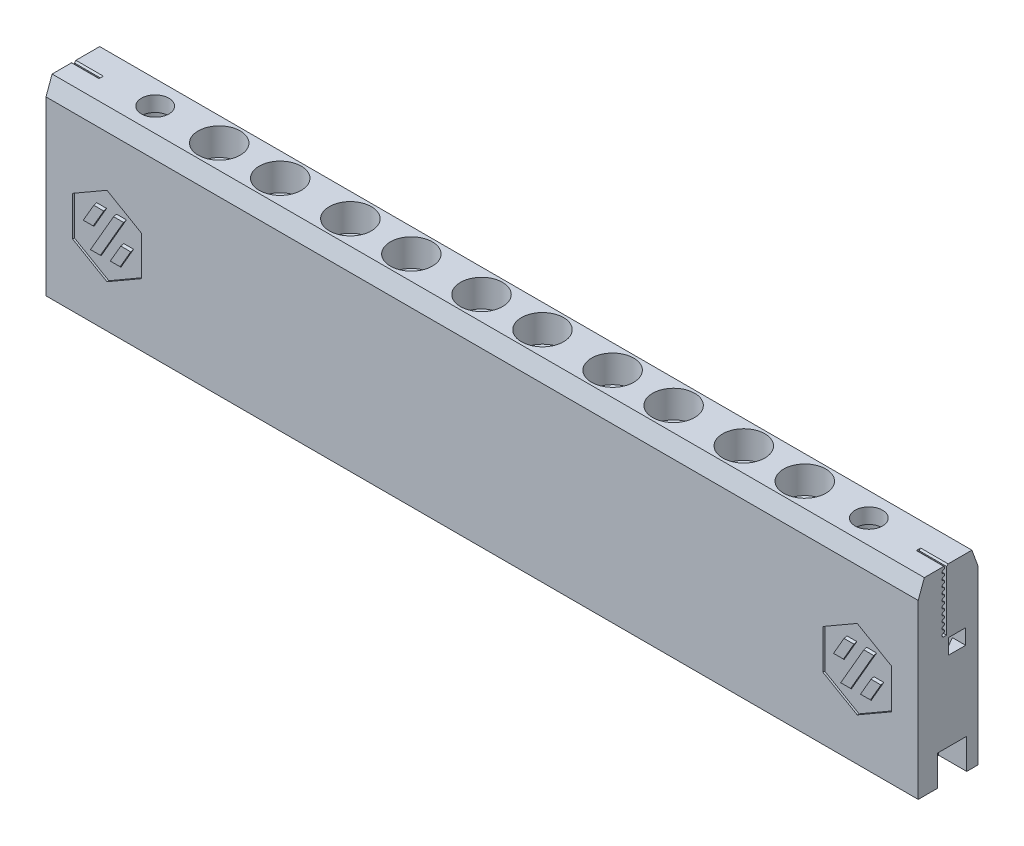
SolidWorks part; units mm, degrees
material "ABS"
ref_plane "Ebene vorne" through (0, 0, 0) normal (0, 0, 1) x (1, 0, 0)
ref_plane "Ebene oben" through (0, 0, 0) normal (0, 1, 0) x (1, 0, 0)
ref_plane "Ebene rechts" through (0, 0, 0) normal (1, 0, 0) x (0, 0, -1)
sketch "Skizze1" plane through (0, 0, 0) normal (0, 1, 0) x (1, 0, 0)
  line L0 (0, 9.8) -> (286, 9.8) construction
  line L1 (0, 0) -> (286, 0)
  line L2 (0, 0) -> (0, 19.6)
  line L3 (0, 19.6) -> (286, 19.6)
  line L4 (286, 0) -> (286, 19.6)
  line L5 (143, 19.6) -> (143, 0) construction
  line L6 (0, 19.6) -> (0, 2.9) construction
  line L7 (0, 2.9) -> (6, 2.9) construction
  line L11 (6, 19.8) -> (6, 2.9) construction
  line L12 (378, 39.8) -> (378, 19.8) construction
  line L13 (-112, 39.8) -> (-92, 39.8) construction
  line L14 (3, 19.8) -> (9, 19.8) construction
  line L15 (3, 19.8) -> (3, 39.8) construction
  line L16 (3, 39.8) -> (9, 39.8) construction
  line L17 (9, 19.8) -> (9, 39.8) construction
  line L18 (-112, 39.8) -> (-112, 19.8) construction
  line L19 (-112, 19.8) -> (-92, 19.8) construction
  line L20 (-92, 39.8) -> (-92, 19.8) construction
  line L21 (398, 19.8) -> (378, 19.8) construction
  line L22 (398, 39.8) -> (398, 19.8) construction
  line L23 (398, 39.8) -> (378, 39.8) construction
  line L24 (277, 19.8) -> (277, 39.8) construction
  line L25 (283, 39.8) -> (277, 39.8) construction
  line L26 (283, 19.8) -> (283, 39.8) construction
  line L27 (283, 19.8) -> (277, 19.8) construction
  line L29 (51.9075, 1.3) -> (56.815, 9.8) construction
  line L30 (56.815, 9.8) -> (51.9075, 18.3) construction
  line L31 (51.9075, 18.3) -> (42.0925, 18.3) construction
  line L32 (42.0925, 18.3) -> (37.185, 9.8) construction
  line L33 (37.185, 9.8) -> (42.0925, 1.3) construction
  line L34 (42.0925, 1.3) -> (51.9075, 1.3) construction
  circle A0 centre (26, 9.8) radius 4.5
  circle A1 centre (260, 9.8) radius 4.5
  circle A2 centre (47, 9.8) radius 4.2
  circle A3 centre (239, 9.8) radius 4.2
  circle A4 centre (67, 9.8) radius 4.2
  circle A5 centre (219, 9.8) radius 4.2
  circle A6 centre (26, 9.8) radius 7.9 construction
  circle A7 centre (90, 9.8) radius 4.2
  circle A8 centre (110, 9.8) radius 4.2
  circle A9 centre (133, 9.8) radius 4.2
  circle A10 centre (153, 9.8) radius 4.2
  circle A11 centre (176, 9.8) radius 4.2
  circle A12 centre (196, 9.8) radius 4.2
  circle A13 centre (47, 9.8) radius 8.5 construction
  point P59 (30.5, 9.8)
  point P61 (33.9, 9.8)
  dimension "D1" = 9
  dimension "D6" = 20
  dimension "D9" = 8.4
  dimension "D10" = 17
  dimension "D11" = 23
  dimension "D13" = 470
  dimension "D20" = 118
  dimension "D23" = 20
  dimension "D24" = 15.8
  dimension "D2" = 19.6
  dimension "D3" = 286
  dimension "D4" = 3
  dimension "D5" = 16.7
  dimension "D7" = 20
  dimension "D8" = 20
  dimension "D12" = 20
  dimension "D14" = 20
  dimension "D15" = 10
  dimension "D16" = 6
  dimension "D17" = 280
  dimension "D18" = 20
  dimension "D19" = 23
  dimension "D21" = 9
  dimension "D25" = 17
  dimension "D26" = 3.285
  dimension "D27" = 1.3
extrude "Aufsatz-Linear austragen1" add sketch "Skizze1" along normal blind 31
sketch "Skizze2" plane through (0, 31, 0) normal (0, 1, 0) x (1, 0, 0)
  line L0 (286, 19.6) -> (0, 19.6) construction
  line L1 (0, 19.6) -> (0, 0) construction
  line L2 (0, 15.9) -> (9.2, 15.9)
  line L3 (0, 15.9) -> (0, 6.26)
  line L4 (0, 6.26) -> (9.2, 6.26)
  line L5 (9.2, 15.9) -> (9.2, 6.26)
  line L6 (143, 19.6) -> (143, 0) construction
  line L7 (0, 0) -> (286, 0) construction
  line L8 (276.8, 15.9) -> (276.8, 6.26)
  line L9 (286, 6.26) -> (276.8, 6.26)
  line L10 (286, 15.9) -> (286, 6.26)
  line L11 (286, 15.9) -> (276.8, 15.9)
  dimension "D1" = 3.7
  dimension "D2" = 9.2
  dimension "D3" = 9.64
extrude "Schnitt-Linear austragen1" cut sketch "Skizze2" against normal blind 20
sketch "Skizze3" plane through (0, 11, 0) normal (0, 1, 0) x (1, 0, 0)
  line L0 (0, 19.6) -> (0, 0) construction
  line L2 (0, 0) -> (286, 0) construction
  line L3 (0, 0) -> (286, 0) construction
  line L4 (143, 0) -> (143, 19.6) construction
  line L6 (286, 19.6) -> (0, 19.6) construction
  circle A0 centre (6, 12.7) radius 1.65
  circle A1 centre (280, 12.7) radius 1.65
  dimension "D1" = 3.3
  dimension "D3" = 6.9
  dimension "D2" = 6
extrude "Schnitt-Linear austragen2" cut sketch "Skizze3" against normal up to surface (11 mm away) up to face at (176, 0, -14)
mirror "Spiegeln3" about plane through (0, 0, -19.6) normal (0, -1, 0) of "Schnitt-Linear austragen2", "Schnitt-Linear austragen1", "Aufsatz-Linear austragen1"
chamfer "Fase1" distance 2 angle 70 2 edges at (143, 31, 0) (143, 31, -19.6)
sketch "Skizze8" plane through (0, 31, 0) normal (0, 1, 0) x (1, 0, 0)
  circle A0 centre (47, 9.8) radius 6.9
  circle A1 centre (67, 9.8) radius 6.9
  circle A2 centre (219, 9.8) radius 6.9
  circle A3 centre (239, 9.8) radius 6.9
  circle A4 centre (90, 9.8) radius 6.9
  circle A5 centre (110, 9.8) radius 6.9
  circle A6 centre (133, 9.8) radius 6.9
  circle A7 centre (153, 9.8) radius 6.9
  circle A8 centre (176, 9.8) radius 6.9
  circle A9 centre (196, 9.8) radius 6.9
  dimension "D1" = 13.8
extrude "Schnitt-Linear austragen6" cut sketch "Skizze8" against normal blind 9
sketch "Skizze9" plane through (0, 31, 0) normal (0, 1, 0) x (1, 0, 0)
  line L0 (42.0925, 18.3) -> (71.9075, 18.3)
  line L1 (71.9075, 18.3) -> (76.815, 9.8)
  line L2 (76.815, 9.8) -> (71.9075, 1.3)
  line L3 (71.9075, 1.3) -> (42.0925, 1.3)
  line L4 (85.0925, 18.3) -> (114.9075, 18.3)
  line L5 (42.0925, 1.3) -> (37.185, 9.8)
  line L6 (214.0925, 18.3) -> (243.9075, 18.3)
  line L7 (243.9075, 18.3) -> (248.815, 9.8)
  line L8 (37.185, 9.8) -> (42.0925, 18.3)
  line L9 (76.815, 9.8) -> (37.185, 9.8) construction
  line L10 (47, 9.8) -> (39.6388, 14.05) construction
  line L11 (67, 9.8) -> (74.3612, 14.05) construction
  line L12 (114.9075, 18.3) -> (119.815, 9.8)
  line L13 (119.815, 9.8) -> (114.9075, 1.3)
  line L14 (114.9075, 1.3) -> (85.0925, 1.3)
  line L15 (85.0925, 1.3) -> (80.185, 9.8)
  line L16 (80.185, 9.8) -> (85.0925, 18.3)
  line L17 (119.815, 9.8) -> (80.185, 9.8) construction
  line L18 (90, 9.8) -> (82.6388, 14.05) construction
  line L19 (110, 9.8) -> (117.3612, 14.05) construction
  line L20 (128.0925, 18.3) -> (157.9075, 18.3)
  line L21 (157.9075, 18.3) -> (162.815, 9.8)
  line L22 (162.815, 9.8) -> (157.9075, 1.3)
  line L23 (157.9075, 1.3) -> (128.0925, 1.3)
  line L24 (128.0925, 1.3) -> (123.185, 9.8)
  line L25 (123.185, 9.8) -> (128.0925, 18.3)
  line L26 (162.815, 9.8) -> (123.185, 9.8) construction
  line L27 (133, 9.8) -> (125.6388, 14.05) construction
  line L28 (153, 9.8) -> (160.3612, 14.05) construction
  line L29 (171.0925, 18.3) -> (200.9075, 18.3)
  line L30 (200.9075, 18.3) -> (205.815, 9.8)
  line L31 (205.815, 9.8) -> (200.9075, 1.3)
  line L32 (200.9075, 1.3) -> (171.0925, 1.3)
  line L33 (171.0925, 1.3) -> (166.185, 9.8)
  line L34 (166.185, 9.8) -> (171.0925, 18.3)
  line L35 (205.815, 9.8) -> (166.185, 9.8) construction
  line L36 (176, 9.8) -> (168.6388, 14.05) construction
  line L37 (196, 9.8) -> (203.3612, 14.05) construction
  line L38 (248.815, 9.8) -> (243.9075, 1.3)
  line L39 (243.9075, 1.3) -> (214.0925, 1.3)
  line L40 (214.0925, 1.3) -> (209.185, 9.8)
  line L41 (209.185, 9.8) -> (214.0925, 18.3)
  line L42 (248.815, 9.8) -> (209.185, 9.8) construction
  line L43 (219, 9.8) -> (211.6388, 14.05) construction
  line L44 (239, 9.8) -> (246.3612, 14.05) construction
  circle A0 centre (47, 9.8) radius 4.2 construction
  circle A1 centre (47, 9.8) radius 4.2 construction
  circle A2 centre (90, 9.8) radius 4.2 construction
  circle A3 centre (133, 9.8) radius 4.2 construction
  circle A4 centre (176, 9.8) radius 4.2 construction
  circle A5 centre (90, 9.8) radius 4.2 construction
  circle A6 centre (110, 9.8) radius 4.2 construction
  circle A7 centre (153, 9.8) radius 4.2 construction
  circle A8 centre (196, 9.8) radius 4.2 construction
  circle A9 centre (239, 9.8) radius 4.2 construction
  circle A10 centre (110, 9.8) radius 4.2 construction
  circle A11 centre (153, 9.8) radius 4.2 construction
  circle A12 centre (196, 9.8) radius 4.2 construction
  circle A13 centre (239, 9.8) radius 4.2 construction
  circle A14 centre (133, 9.8) radius 4.2 construction
  circle A15 centre (176, 9.8) radius 4.2 construction
  circle A16 centre (219, 9.8) radius 4.2 construction
  circle A17 centre (219, 9.8) radius 4.2 construction
  point P12 (67, 9.8)
  point P23 (110, 9.8)
  point P36 (153, 9.8)
  point P49 (196, 9.8)
  point P73 (239, 9.8)
  dimension "D1" = 17
  dimension "D2" = 120
  dimension "D3" = 17
  dimension "D4" = 120
  dimension "D5" = 17
  dimension "D6" = 120
  dimension "D7" = 17
  dimension "D8" = 120
  dimension "D9" = 17
  dimension "D10" = 120
extrude "Schnitt-Linear austragen7" cut sketch "Skizze9" against normal up to surface (47 mm away) from offset 15 up to face at (176, -31, -14)
sketch "Skizze13" plane through (0, -31, 0) normal (0, -1, 0) x (1, 0, 0)
  circle A0 centre (26, -9.8) radius 7.65
  circle A1 centre (260, -9.8) radius 7.65
  dimension "D1" = 15.3
extrude "Schnitt-Linear austragen10" cut sketch "Skizze13" against normal offset from surface (57 mm away) 5 up to face at (196, 31, -2.9)
sketch "Skizze17" plane through (0, 22, 0) normal (0, 1, 0) x (1, 0, 0)
  circle A0 centre (47, 9.8) radius 4.2 construction
  circle A1 centre (67, 9.8) radius 4.2 construction
  circle A2 centre (90, 9.8) radius 4.2 construction
  circle A3 centre (110, 9.8) radius 4.2 construction
  circle A4 centre (133, 9.8) radius 4.2 construction
  circle A6 centre (153, 9.8) radius 4.2 construction
  circle A7 centre (176, 9.8) radius 4.2 construction
  circle A8 centre (196, 9.8) radius 4.2 construction
  circle A9 centre (219, 9.8) radius 4.2 construction
  circle A10 centre (239, 9.8) radius 4.2 construction
  circle A11 centre (47, 9.8) radius 4.2
  circle A12 centre (67, 9.8) radius 4.2
  circle A13 centre (90, 9.8) radius 4.2
  circle A14 centre (110, 9.8) radius 4.2
  circle A15 centre (133, 9.8) radius 4.2
  circle A17 centre (153, 9.8) radius 4.2
  circle A18 centre (176, 9.8) radius 4.2
  circle A19 centre (196, 9.8) radius 4.2
  circle A20 centre (219, 9.8) radius 4.2
  circle A21 centre (239, 9.8) radius 4.2
extrude "Aufsatz-Linear austragen2" add sketch "Skizze17" against normal blind 0.4
sketch "Skizze19" plane through (0, 31, 0) normal (0, 1, 0) x (1, 0, 0)
  line L0 (0, 6.26) -> (0, 2) construction
  line L1 (9.2, 6.26) -> (0, 6.26)
  line L2 (9.2, 6.26) -> (9.2, 15.9)
  line L3 (9.2, 15.9) -> (0, 15.9)
  line L4 (0, 6.26) -> (0, 15.9)
  line L5 (9.2, 6.26) -> (9.2, 15.9) construction
  line L8 (286, 15.9) -> (286, 17.6) construction
  line L9 (286, 6.26) -> (276.8, 6.26)
  line L10 (286, 6.26) -> (286, 15.9)
  line L11 (286, 15.9) -> (276.8, 15.9)
  line L12 (276.8, 6.26) -> (276.8, 15.9)
  line L13 (276.8, 15.9) -> (276.8, 6.26) construction
  line L14 (9.2, 15.9) -> (0, 15.9) construction
  line L15 (0, 6.26) -> (9.2, 6.26) construction
  line L16 (286, 15.9) -> (276.8, 15.9) construction
  line L17 (276.8, 6.26) -> (286, 6.26) construction
  circle A0 centre (280, 12.7) radius 1.65 construction
  circle A1 centre (6, 12.7) radius 1.65 construction
  circle A2 centre (280, 12.7) radius 1.65
  circle A3 centre (6, 12.7) radius 1.65
extrude "Aufsatz-Linear austragen3" add sketch "Skizze19" against normal up to surface (20 mm away) up to face at (6, 11, -11.05)
sketch "Skizze22" plane through (0, 0, 0) normal (-1, 0, 0) x (0, 0, 1)
  line L0 (-17.6, 31) -> (-2, 31) construction
  line L1 (-8.55, 28.31) -> (-8.55, 28.81)
  line L2 (-10.05, 30.31) -> (-10.05, 30.81) construction
  line L3 (-8.55, 30.31) -> (-8.55, 30.81)
  line L4 (-9.3, 31) -> (-8.36, 31)
  line L5 (-8.55, 26.31) -> (-8.55, 26.81)
  line L6 (-8.55, 24.31) -> (-8.55, 24.81)
  line L7 (-8.55, 22.31) -> (-8.55, 22.81)
  line L8 (-8.55, 20.31) -> (-8.55, 20.81)
  line L9 (-8.55, 18.31) -> (-8.55, 18.81)
  line L10 (-8.55, 16.31) -> (-8.55, 16.81)
  line L11 (-8.55, 14.31) -> (-8.55, 14.81)
  line L12 (-8.55, 12.31) -> (-8.55, 12.81)
  line L13 (0, 25.505) -> (0, -31) construction
  line L14 (-9.3, 11) -> (-8.36, 11)
  line L18 (-9.3, 31) -> (-9.3, 11)
  arc A0 (-10.24, 30.12) -> (-10.24, 29) centre (-10.24, 29.56) ccw construction
  arc A1 (-8.36, 30.12) -> (-8.36, 29) centre (-8.36, 29.56) cw
  arc A2 (-8.55, 30.31) -> (-8.36, 30.12) centre (-8.36, 30.31) ccw
  arc A3 (-8.36, 31) -> (-8.55, 30.81) centre (-8.36, 30.81) ccw
  arc A4 (-10.05, 30.31) -> (-10.24, 30.12) centre (-10.24, 30.31) cw construction
  arc A5 (-10.24, 31) -> (-10.05, 30.81) centre (-10.24, 30.81) cw construction
  arc A6 (-8.36, 29) -> (-8.55, 28.81) centre (-8.36, 28.81) ccw
  arc A7 (-8.55, 28.31) -> (-8.36, 28.12) centre (-8.36, 28.31) ccw
  arc A8 (-8.36, 28.12) -> (-8.36, 27) centre (-8.36, 27.56) cw
  arc A9 (-8.36, 27) -> (-8.55, 26.81) centre (-8.36, 26.81) ccw
  arc A10 (-8.55, 26.31) -> (-8.36, 26.12) centre (-8.36, 26.31) ccw
  arc A11 (-8.36, 26.12) -> (-8.36, 25) centre (-8.36, 25.56) cw
  arc A12 (-8.36, 25) -> (-8.55, 24.81) centre (-8.36, 24.81) ccw
  arc A13 (-8.55, 24.31) -> (-8.36, 24.12) centre (-8.36, 24.31) ccw
  arc A14 (-8.36, 24.12) -> (-8.36, 23) centre (-8.36, 23.56) cw
  arc A15 (-8.36, 23) -> (-8.55, 22.81) centre (-8.36, 22.81) ccw
  arc A16 (-8.55, 22.31) -> (-8.36, 22.12) centre (-8.36, 22.31) ccw
  arc A17 (-8.36, 22.12) -> (-8.36, 21) centre (-8.36, 21.56) cw
  arc A18 (-8.36, 21) -> (-8.55, 20.81) centre (-8.36, 20.81) ccw
  arc A19 (-8.55, 20.31) -> (-8.36, 20.12) centre (-8.36, 20.31) ccw
  arc A20 (-8.36, 20.12) -> (-8.36, 19) centre (-8.36, 19.56) cw
  arc A21 (-8.36, 19) -> (-8.55, 18.81) centre (-8.36, 18.81) ccw
  arc A22 (-8.55, 18.31) -> (-8.36, 18.12) centre (-8.36, 18.31) ccw
  arc A23 (-8.36, 18.12) -> (-8.36, 17) centre (-8.36, 17.56) cw
  arc A24 (-8.36, 17) -> (-8.55, 16.81) centre (-8.36, 16.81) ccw
  arc A25 (-8.55, 16.31) -> (-8.36, 16.12) centre (-8.36, 16.31) ccw
  arc A26 (-8.36, 16.12) -> (-8.36, 15) centre (-8.36, 15.56) cw
  arc A27 (-8.36, 15) -> (-8.55, 14.81) centre (-8.36, 14.81) ccw
  arc A28 (-8.55, 14.31) -> (-8.36, 14.12) centre (-8.36, 14.31) ccw
  arc A29 (-8.36, 14.12) -> (-8.36, 13) centre (-8.36, 13.56) cw
  arc A30 (-8.36, 13) -> (-8.55, 12.81) centre (-8.36, 12.81) ccw
  arc A31 (-8.55, 12.31) -> (-8.36, 12.12) centre (-8.36, 12.31) ccw
  arc A32 (-8.36, 12.12) -> (-8.36, 11) centre (-8.36, 11.56) cw
  point P5 (-10.8, 29.56)
  dimension "D1" = 0.56
  dimension "D2" = 2
  dimension "D3" = 0.75
  dimension "D4" = 20
  dimension "D5" = 1.5
  dimension "D6" = 10
  dimension "D7" = 9.3
extrude "Schnitt-Linear austragen14" cut sketch "Skizze22" against normal blind 9
sketch "Skizze23" plane through (286, 0, 0) normal (1, 0, 0) x (0, 0, -1)
  line L13 (8.55, 30.81) -> (8.55, 30.31)
  line L14 (9.3, 31) -> (8.36, 31)
  line L15 (9.3, 11) -> (9.3, 31)
  line L16 (8.36, 11) -> (9.3, 11)
  line L17 (8.55, 12.81) -> (8.55, 12.31)
  line L18 (8.55, 14.81) -> (8.55, 14.31)
  line L19 (8.55, 16.81) -> (8.55, 16.31)
  line L20 (8.55, 18.81) -> (8.55, 18.31)
  line L21 (8.55, 20.81) -> (8.55, 20.31)
  line L22 (8.55, 22.81) -> (8.55, 22.31)
  line L23 (8.55, 24.81) -> (8.55, 24.31)
  line L24 (8.55, 26.81) -> (8.55, 26.31)
  line L25 (8.55, 28.81) -> (8.55, 28.31)
  line L26 (8.55, 30.81) -> (8.55, 30.31)
  line L27 (9.3, 31) -> (8.36, 31)
  line L28 (9.3, 11) -> (9.3, 31)
  line L29 (8.36, 11) -> (9.3, 11)
  line L30 (8.55, 12.81) -> (8.55, 12.31)
  line L31 (8.55, 14.81) -> (8.55, 14.31)
  line L32 (8.55, 16.81) -> (8.55, 16.31)
  line L33 (8.55, 18.81) -> (8.55, 18.31)
  line L34 (8.55, 20.81) -> (8.55, 20.31)
  line L35 (8.55, 22.81) -> (8.55, 22.31)
  line L36 (8.55, 24.81) -> (8.55, 24.31)
  line L37 (8.55, 26.81) -> (8.55, 26.31)
  line L38 (8.55, 28.81) -> (8.55, 28.31)
  arc A30 (8.36, 30.12) -> (8.55, 30.31) centre (8.36, 30.31) ccw
  arc A31 (8.55, 30.81) -> (8.36, 31) centre (8.36, 30.81) ccw
  arc A32 (8.36, 12.12) -> (8.36, 11) centre (8.36, 11.56) ccw
  arc A33 (8.36, 12.12) -> (8.55, 12.31) centre (8.36, 12.31) ccw
  arc A34 (8.55, 12.81) -> (8.36, 13) centre (8.36, 12.81) ccw
  arc A35 (8.36, 14.12) -> (8.36, 13) centre (8.36, 13.56) ccw
  arc A36 (8.36, 14.12) -> (8.55, 14.31) centre (8.36, 14.31) ccw
  arc A37 (8.55, 14.81) -> (8.36, 15) centre (8.36, 14.81) ccw
  arc A38 (8.36, 16.12) -> (8.36, 15) centre (8.36, 15.56) ccw
  arc A39 (8.36, 16.12) -> (8.55, 16.31) centre (8.36, 16.31) ccw
  arc A40 (8.55, 16.81) -> (8.36, 17) centre (8.36, 16.81) ccw
  arc A41 (8.36, 18.12) -> (8.36, 17) centre (8.36, 17.56) ccw
  arc A42 (8.36, 18.12) -> (8.55, 18.31) centre (8.36, 18.31) ccw
  arc A43 (8.55, 18.81) -> (8.36, 19) centre (8.36, 18.81) ccw
  arc A44 (8.36, 20.12) -> (8.36, 19) centre (8.36, 19.56) ccw
  arc A45 (8.36, 20.12) -> (8.55, 20.31) centre (8.36, 20.31) ccw
  arc A46 (8.55, 20.81) -> (8.36, 21) centre (8.36, 20.81) ccw
  arc A47 (8.36, 22.12) -> (8.36, 21) centre (8.36, 21.56) ccw
  arc A48 (8.36, 22.12) -> (8.55, 22.31) centre (8.36, 22.31) ccw
  arc A49 (8.55, 22.81) -> (8.36, 23) centre (8.36, 22.81) ccw
  arc A50 (8.36, 24.12) -> (8.36, 23) centre (8.36, 23.56) ccw
  arc A51 (8.36, 24.12) -> (8.55, 24.31) centre (8.36, 24.31) ccw
  arc A52 (8.55, 24.81) -> (8.36, 25) centre (8.36, 24.81) ccw
  arc A53 (8.36, 26.12) -> (8.36, 25) centre (8.36, 25.56) ccw
  arc A54 (8.36, 26.12) -> (8.55, 26.31) centre (8.36, 26.31) ccw
  arc A55 (8.55, 26.81) -> (8.36, 27) centre (8.36, 26.81) ccw
  arc A56 (8.36, 28.12) -> (8.36, 27) centre (8.36, 27.56) ccw
  arc A57 (8.36, 28.12) -> (8.55, 28.31) centre (8.36, 28.31) ccw
  arc A58 (8.55, 28.81) -> (8.36, 29) centre (8.36, 28.81) ccw
  arc A59 (8.36, 30.12) -> (8.36, 29) centre (8.36, 29.56) ccw
  arc A60 (8.36, 30.12) -> (8.55, 30.31) centre (8.36, 30.31) ccw
  arc A61 (8.55, 30.81) -> (8.36, 31) centre (8.36, 30.81) ccw
  arc A62 (8.36, 12.12) -> (8.36, 11) centre (8.36, 11.56) ccw
  arc A63 (8.36, 12.12) -> (8.55, 12.31) centre (8.36, 12.31) ccw
  arc A64 (8.55, 12.81) -> (8.36, 13) centre (8.36, 12.81) ccw
  arc A65 (8.36, 14.12) -> (8.36, 13) centre (8.36, 13.56) ccw
  arc A66 (8.36, 14.12) -> (8.55, 14.31) centre (8.36, 14.31) ccw
  arc A67 (8.55, 14.81) -> (8.36, 15) centre (8.36, 14.81) ccw
  arc A68 (8.36, 16.12) -> (8.36, 15) centre (8.36, 15.56) ccw
  arc A69 (8.36, 16.12) -> (8.55, 16.31) centre (8.36, 16.31) ccw
  arc A70 (8.55, 16.81) -> (8.36, 17) centre (8.36, 16.81) ccw
  arc A71 (8.36, 18.12) -> (8.36, 17) centre (8.36, 17.56) ccw
  arc A72 (8.36, 18.12) -> (8.55, 18.31) centre (8.36, 18.31) ccw
  arc A73 (8.55, 18.81) -> (8.36, 19) centre (8.36, 18.81) ccw
  arc A74 (8.36, 20.12) -> (8.36, 19) centre (8.36, 19.56) ccw
  arc A75 (8.36, 20.12) -> (8.55, 20.31) centre (8.36, 20.31) ccw
  arc A76 (8.55, 20.81) -> (8.36, 21) centre (8.36, 20.81) ccw
  arc A77 (8.36, 22.12) -> (8.36, 21) centre (8.36, 21.56) ccw
  arc A78 (8.36, 22.12) -> (8.55, 22.31) centre (8.36, 22.31) ccw
  arc A79 (8.55, 22.81) -> (8.36, 23) centre (8.36, 22.81) ccw
  arc A80 (8.36, 24.12) -> (8.36, 23) centre (8.36, 23.56) ccw
  arc A81 (8.36, 24.12) -> (8.55, 24.31) centre (8.36, 24.31) ccw
  arc A82 (8.55, 24.81) -> (8.36, 25) centre (8.36, 24.81) ccw
  arc A83 (8.36, 26.12) -> (8.36, 25) centre (8.36, 25.56) ccw
  arc A84 (8.36, 26.12) -> (8.55, 26.31) centre (8.36, 26.31) ccw
  arc A85 (8.55, 26.81) -> (8.36, 27) centre (8.36, 26.81) ccw
  arc A86 (8.36, 28.12) -> (8.36, 27) centre (8.36, 27.56) ccw
  arc A87 (8.36, 28.12) -> (8.55, 28.31) centre (8.36, 28.31) ccw
  arc A88 (8.55, 28.81) -> (8.36, 29) centre (8.36, 28.81) ccw
  arc A89 (8.36, 30.12) -> (8.36, 29) centre (8.36, 29.56) ccw
  dimension "D1" = 0
extrude "Schnitt-Linear austragen15" cut sketch "Skizze23" against normal blind 9
sketch "Skizze25" plane through (0, 31, 0) normal (0, 1, 0) x (1, 0, 0)
  circle A0 centre (6, 12.7) radius 1.65 construction
  circle A1 centre (280, 12.7) radius 1.65 construction
  circle A2 centre (6, 12.7) radius 1.65
  circle A3 centre (280, 12.7) radius 1.65
extrude "Aufsatz-Linear austragen4" add sketch "Skizze25" against normal offset from surface (17 mm away) 25 up to face at (6, -11, -11.05)
sketch "Skizze26" plane through (0, 0, 0) normal (0, 0, 1) x (1, 0, 0)
  line L0 (22.5159, 3.1702) -> (25.7635, 3.1702)
  line L1 (25.7635, 3.1702) -> (17.4841, -11.1702)
  line L2 (17.4841, -11.1702) -> (14.2365, -11.1702)
  line L3 (14.2365, -11.1702) -> (22.5159, 3.1702)
  line L4 (16.0207, 3.1702) -> (19.2683, 3.1702)
  line L5 (19.2683, 3.1702) -> (15.1286, -4)
  line L6 (15.1286, -4) -> (11.881, -4)
  line L7 (11.881, -4) -> (16.0207, 3.1702)
  line L8 (24.8714, -4) -> (20.7317, -11.1702)
  line L9 (20.7317, -11.1702) -> (23.9793, -11.1702)
  line L10 (23.9793, -11.1702) -> (28.119, -4)
  line L11 (28.119, -4) -> (24.8714, -4)
  line L12 (25.625, 5.7428) -> (14.375, -13.7428) construction
  line L13 (31.25, 2.4952) -> (20, 8.9904)
  line L14 (20, 8.9904) -> (8.75, 2.4952)
  line L15 (8.75, 2.4952) -> (8.75, -10.4952)
  line L16 (8.75, -10.4952) -> (20, -16.9904)
  line L17 (20, -16.9904) -> (31.25, -10.4952)
  line L18 (31.25, -10.4952) -> (31.25, 2.4952)
  line L19 (24.8714, -4) -> (21.6238, -4) construction
  line L20 (15.1286, -4) -> (18.3762, -4) construction
  line L21 (8.75, -4) -> (0, -4) construction
  line L22 (8.75, -4) -> (20, -4) construction
  line L23 (23.9793, -11.1702) -> (23.9793, -10.4952) construction
  line L24 (25.7635, 3.1702) -> (25.7635, 2.4952) construction
  line L26 (0, 25.505) -> (0, -31) construction
  line L27 (0, 31) -> (286, 31) construction
  line L28 (268.5159, 3.1702) -> (271.7635, 3.1702)
  line L29 (271.7635, 3.1702) -> (263.4841, -11.1702)
  line L30 (263.4841, -11.1702) -> (260.2365, -11.1702)
  line L31 (260.2365, -11.1702) -> (268.5159, 3.1702)
  line L32 (262.0207, 3.1702) -> (265.2683, 3.1702)
  line L33 (265.2683, 3.1702) -> (261.1286, -4)
  line L34 (261.1286, -4) -> (257.881, -4)
  line L35 (257.881, -4) -> (262.0207, 3.1702)
  line L36 (270.8714, -4) -> (266.7317, -11.1702)
  line L37 (266.7317, -11.1702) -> (269.9793, -11.1702)
  line L38 (269.9793, -11.1702) -> (274.119, -4)
  line L39 (274.119, -4) -> (270.8714, -4)
  line L40 (271.625, 5.7428) -> (260.375, -13.7428) construction
  line L41 (277.25, 2.4952) -> (266, 8.9904)
  line L42 (266, 8.9904) -> (254.75, 2.4952)
  line L43 (254.75, 2.4952) -> (254.75, -10.4952)
  line L44 (254.75, -10.4952) -> (266, -16.9904)
  line L45 (266, -16.9904) -> (277.25, -10.4952)
  line L46 (277.25, -10.4952) -> (277.25, 2.4952)
  line L47 (270.8714, -4) -> (267.6238, -4) construction
  line L48 (261.1286, -4) -> (264.3762, -4) construction
  line L49 (277.25, -4) -> (286, -4) construction
  line L50 (254.75, -4) -> (266, -4) construction
  line L51 (269.9793, -11.1702) -> (269.9793, -10.4952) construction
  line L52 (271.7635, 3.1702) -> (271.7635, 2.4952) construction
  line L53 (286, 25.505) -> (286, -31) construction
  circle A0 centre (20, -4) radius 11.25 construction
  circle A1 centre (266, -4) radius 11.25 construction
  point P22 (24.1397, 3.1702)
  point P55 (270.1397, 3.1702)
  dimension "D1" = 22.5
  dimension "D2" = 2.8125
  dimension "D3" = 0.675
  dimension "D4" = 35
  dimension "D5" = 20
  dimension "D6" = 22.5
  dimension "D7" = 2.8125
  dimension "D8" = 0.675
  dimension "D9" = 35
  dimension "D10" = 20
extrude "Schnitt-Linear austragen16" cut sketch "Skizze26" against normal blind 0.6
chamfer "Fase2" distance 0.6 angle 45 12 edges at (261.8603, -11.1702, 0) (268.3555, -11.1702, 0) (272.4952, -4, 0) (270.1397, 3.1702, 0) (263.6445, 3.1702, 0) (259.5048, -4, 0) (26.4952, -4, 0) (22.3555, -11.1702, 0) (15.8603, -11.1702, 0) (24.1397, 3.1702, 0) (17.6445, 3.1702, 0) (13.5048, -4, 0)
chamfer "Fase3" distance 0.5 angle 45 2 edges at (4.5, 31, -9.3) (281.5, 31, -9.3)
sketch "Skizze27" plane through (0, -31, 0) normal (0, -1, 0) x (1, 0, 0)
  line L0 (9.2, -9.8) -> (276.8, -9.8) construction
  line L1 (9.2, -6.26) -> (9.2, -15.9) construction
  line L2 (276.8, -15.9) -> (276.8, -6.26) construction
  line L3 (272, -9.8) -> (272, -13.8) construction
  line L4 (14, -5.8) -> (14, -9.8) construction
  line L5 (0, -6.26) -> (0, 0) construction
  line L6 (286, 0) -> (286, -6.26) construction
  line L7 (78.5, -13.8) -> (78.5, -9.8) construction
  line L8 (121.5, -9.8) -> (121.5, -5.8) construction
  line L9 (164.5, -9.8) -> (164.5, -13.8) construction
  line L10 (207.5, -9.8) -> (207.5, -5.8) construction
  circle A0 centre (14, -5.8) radius 2.25
  circle A1 centre (272, -13.8) radius 2.25
  circle A2 centre (78.5, -13.8) radius 2.25
  circle A3 centre (121.5, -5.8) radius 2.25
  circle A4 centre (164.5, -13.8) radius 2.25
  circle A5 centre (207.5, -5.8) radius 2.25
  dimension "D1" = 4.5
  dimension "D2" = 14
  dimension "D3" = 14
  dimension "D4" = 4
extrude "Schnitt-Linear austragen17" cut sketch "Skizze27" against normal blind 15
sketch "Skizze28" plane through (0, -11, 0) normal (0, -1, 0) x (1, 0, 0)
  line L4 (0, -6.26) -> (0, -15.9)
  line L5 (0, -15.9) -> (9.2, -15.9)
  line L6 (9.2, -15.9) -> (9.2, -6.26)
  line L7 (9.2, -6.26) -> (0, -6.26)
  line L8 (0, -6.26) -> (0, -15.9)
  line L9 (0, -15.9) -> (9.2, -15.9)
  line L10 (9.2, -15.9) -> (9.2, -6.26)
  line L11 (9.2, -6.26) -> (0, -6.26)
  line L12 (276.8, -15.9) -> (286, -15.9)
  line L13 (286, -15.9) -> (286, -6.26)
  line L14 (286, -6.26) -> (276.8, -6.26)
  line L15 (276.8, -6.26) -> (276.8, -15.9)
  line L16 (276.8, -15.9) -> (286, -15.9)
  line L17 (286, -15.9) -> (286, -6.26)
  line L18 (286, -6.26) -> (276.8, -6.26)
  line L19 (276.8, -6.26) -> (276.8, -15.9)
  circle A0 centre (6, -12.7) radius 1.65 construction
  circle A1 centre (6, -12.7) radius 1.65
  circle A2 centre (280, -12.7) radius 1.65 construction
  circle A3 centre (280, -12.7) radius 1.65
  dimension "D1" = 0
  dimension "D2" = 0
extrude "Aufsatz-Linear austragen5" add sketch "Skizze28" along normal blind 10
sketch "Skizze29" plane through (0, -21, 0) normal (0, -1, 0) x (1, 0, 0)
  line L0 (0, -15.9) -> (9.2, -15.9) construction
  line L1 (4.3546, -9.85) -> (2.7091, -12.7)
  line L2 (2.7091, -12.7) -> (4.3546, -15.55)
  line L3 (4.3546, -15.55) -> (7.6454, -15.55)
  line L4 (7.6454, -15.55) -> (9.2909, -12.7)
  line L5 (9.2909, -12.7) -> (7.6454, -9.85)
  line L6 (7.6454, -9.85) -> (4.3546, -9.85)
  line L7 (143, 0) -> (143, -19.6) construction
  line L8 (0, 0) -> (286, 0) construction
  line L9 (286, -19.6) -> (0, -19.6) construction
  line L10 (278.3546, -9.85) -> (281.6454, -9.85)
  line L11 (276.7091, -12.7) -> (278.3546, -9.85)
  line L12 (278.3546, -15.55) -> (276.7091, -12.7)
  line L13 (281.6454, -15.55) -> (278.3546, -15.55)
  line L14 (283.2909, -12.7) -> (281.6454, -15.55)
  line L15 (281.6454, -9.85) -> (283.2909, -12.7)
  circle A0 centre (6, -12.7) radius 2.85 construction
  circle A1 centre (280, -12.7) radius 2.85 construction
  dimension "D1" = 5.7
extrude "Schnitt-Linear austragen18" cut sketch "Skizze29" against normal blind 28 from offset 3
sketch "Skizze30" plane through (0, 10, 0) normal (0, -1, 0) x (1, 0, 0)
  line L0 (4.3546, -15.55) -> (0, -15.55)
  line L1 (0, -15.55) -> (0, -9.85)
  line L2 (0, -9.85) -> (4.3546, -9.85)
  line L3 (4.3546, -9.85) -> (2.7091, -12.7)
  line L4 (2.7091, -12.7) -> (4.3546, -15.55)
  line L5 (0, -6.26) -> (0, -15.9) construction
  line L6 (281.6454, -9.85) -> (286, -9.85)
  line L7 (286, -9.85) -> (286, -15.55)
  line L8 (286, -15.55) -> (281.6454, -15.55)
  line L9 (281.6454, -15.55) -> (283.2909, -12.7)
  line L10 (283.2909, -12.7) -> (281.6454, -9.85)
  line L11 (286, -15.9) -> (286, -6.26) construction
extrude "Schnitt-Linear austragen19" cut sketch "Skizze30" along normal blind 5
sketch "Skizze31" plane through (0, 10, 0) normal (0, -1, 0) x (1, 0, 0)
  circle A0 centre (6, -12.7) radius 1.65 construction
  circle A1 centre (280, -12.7) radius 1.65 construction
  circle A2 centre (6, -12.7) radius 1.65
  circle A3 centre (280, -12.7) radius 1.65
extrude "Aufsatz-Linear austragen6" add sketch "Skizze31" against normal up to surface (4 mm away) up to face at (280, 14, -14.35)
chamfer "Fase4" distance 1.6 angle 45 2 edges at (280, -18, -11.05) (6, -18, -14.35)
